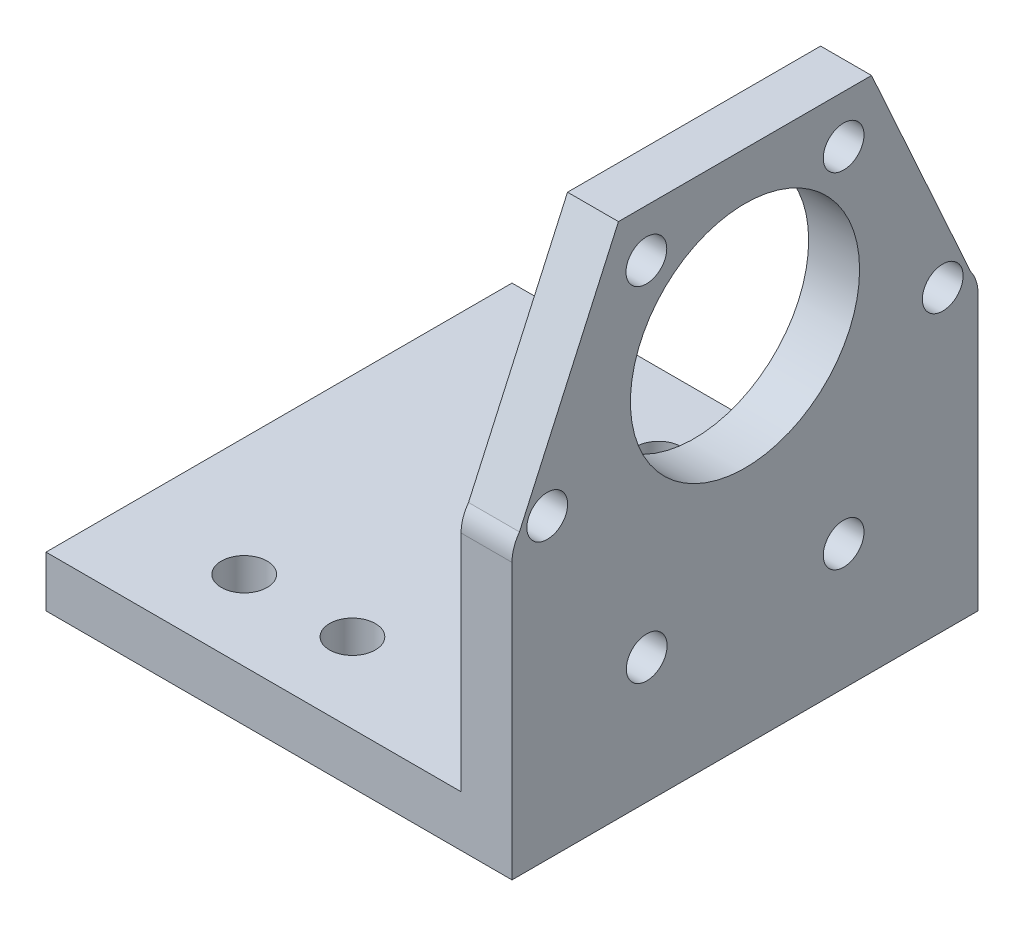
SolidWorks part; units mm, degrees
ref_plane "前视基准面" through (0, 0, 0) normal (0, 0, 1) x (1, 0, 0)
ref_plane "上视基准面" through (0, 0, 0) normal (0, 1, 0) x (1, 0, 0)
ref_plane "右视基准面" through (0, 0, 0) normal (1, 0, 0) x (0, 0, -1)
sketch "草图1" plane through (0, 0, 0) normal (0, 1, 0) x (1, 0, 0)
  line L1 (18.3, -18.3) -> (-18.3, -18.3)
  line L2 (18.3, -18.3) -> (18.3, 18.3)
  line L3 (18.3, 18.3) -> (-18.3, 18.3)
  line L4 (-18.3, -18.3) -> (-18.3, 18.3)
  line L5 (18.3, -18.3) -> (-18.3, 18.3) construction
  line L6 (18.3, 18.3) -> (-18.3, -18.3) construction
  point P0 (0, 0)
  dimension "D1" = 36.6
  dimension "D2" = 36.6
extrude "凸台-拉伸1" add sketch "草图1" along normal blind 40.6
ref_plane "基准面1" through (0, 40.6, 0) normal (0, 1, 0) x (1, 0, 0)
sketch "草图2" plane through (0, 40.6, 0) normal (0, 1, 0) x (1, 0, 0)
  line L0 (-18.3, -18.3) -> (18.3, -18.3) construction
  line L1 (-18.3, 18.3) -> (14.3, 18.3)
  line L2 (-18.3, 18.3) -> (-18.3, -18.3)
  line L3 (-18.3, -18.3) -> (14.3, -18.3)
  line L4 (14.3, 18.3) -> (14.3, -18.3)
  dimension "D1" = 32.6
extrude "切除-拉伸1" cut sketch "草图2" against normal blind 36.6
ref_plane "基准面2" through (18.3, 0, 0) normal (1, 0, 0) x (0, 0, -1)
sketch "草图3" plane through (18.3, 0, 0) normal (1, 0, 0) x (0, 0, -1)
  line L0 (20.13, 40.6) -> (-20.13, 40.6) construction
  line L1 (-18.3, 40.6) -> (18.3, 40.6)
  line L2 (-18.3, 40.6) -> (-18.3, 4)
  line L3 (-18.3, 4) -> (18.3, 4)
  line L4 (18.3, 40.6) -> (18.3, 4)
  line L5 (-18.3, 40.6) -> (-18.3, 0) construction
  line L6 (18.3, 40.6) -> (18.3, 0) construction
  line L7 (0, 40.6) -> (0, 36.8637) construction
  line L8 (0, 36.8637) -> (0, 27.8637) construction
  line L9 (7.7452, 36.8637) -> (-7.7452, 36.8637)
  line L10 (-7.7452, 36.8637) -> (-15.53, 23.3801) construction
  line L11 (7.7452, 36.8637) -> (15.53, 23.3801) construction
  line L12 (-15.53, 23.3801) -> (-7.719, 9.851) construction
  line L13 (-7.719, 9.851) -> (7.7452, 9.851) construction
  line L14 (7.7452, 9.851) -> (15.53, 23.3801) construction
  circle A0 centre (0, 27.8637) radius 9
  circle A1 centre (-7.7452, 36.8637) radius 1.6
  circle A2 centre (7.7452, 36.8637) radius 1.6
  circle A3 centre (-15.53, 23.3801) radius 1.6
  circle A4 centre (15.53, 23.3801) radius 1.6
  circle A5 centre (7.7452, 9.851) radius 1.6
  circle A6 centre (-7.719, 9.851) radius 1.6
  point P10 (0, 40.6)
  point P20 (0, 36.8637)
  dimension "D2" = 120
  dimension "D4" = 18
  dimension "D1" = 36.6
  dimension "D3" = 120
extrude "切除-拉伸5" cut sketch "草图3" against normal blind 36.6 contours A0 | A1 | A3 | A2 | A4 | A5 | A6 region at (18.3, 27.8637, 0) region at (18.3, 36.8637, 9.3) region at (18.3, 38.4184, -7.7452) region at (18.3, 23.3801, 15.53) region at (18.3, 23.3801, -15.53) region at (18.3, 9.851, -7.7452) region at (18.3, 9.851, 7.719)
fillet "圆角2" radius 2 2 edges at (16.3, 40.6, 18.3) (16.3, 40.6, -18.3)
ref_plane "基准面3" through (0, 0, 0) normal (0, -1, 0) x (-1, 0, 0)
sketch "草图7" plane through (0, 0, 0) normal (0, -1, 0) x (-1, 0, 0)
  line L0 (-18.0079, 0) -> (18.3, 0) construction
  line L1 (18.3, 18.3) -> (18.3, -18.3) construction
  circle A0 centre (0.5074, 12.025) radius 1.8
  circle A1 centre (9.0074, 12.025) radius 1.8
  circle A2 centre (9.0074, -12.025) radius 1.8
  circle A3 centre (0.5074, -12.025) radius 1.8
  dimension "D1" = 8.5
  dimension "D2" = 24.05
extrude "切除-拉伸6" cut sketch "草图7" against normal blind 10
sketch "草图12" plane through (18.3, 0, 0) normal (1, 0, 0) x (0, 0, -1)
  line L0 (-9.3452, 36.8637) -> (-18.3, 36.8637) construction
  line L1 (-18.3, 38.6) -> (-18.3, 0) construction
  line L2 (-17.13, 23.3801) -> (-18.3, 23.3801) construction
  line L3 (-17.715, 23.3801) -> (-11.6264, 36.8637)
  line L4 (-11.6264, 36.8637) -> (-9.9392, 40.6)
  line L5 (2.2, 40.6) -> (-2.2, 40.6) construction
  line L6 (-17.715, 23.3801) -> (-18.3, 23.3801)
  line L7 (-18.3, 23.3801) -> (-18.3, 40.6)
  line L8 (-18.3, 40.6) -> (-9.9392, 40.6)
  line L9 (0, 40.6) -> (0, 22.4035) construction
  line L10 (18.3, 23.3801) -> (18.3, 40.6)
  line L11 (17.715, 23.3801) -> (18.3, 23.3801)
  line L12 (17.715, 23.3801) -> (11.6264, 36.8637)
  line L13 (11.6264, 36.8637) -> (9.9392, 40.6)
  line L14 (18.3, 40.6) -> (9.9392, 40.6)
  circle A0 centre (-7.7452, 36.8637) radius 1.6 construction
  circle A1 centre (-15.53, 23.3801) radius 1.6 construction
  point P12 (-17.715, 23.3801)
  point P13 (-13.8226, 36.8637)
extrude "切除-拉伸8" cut sketch "草图12" against normal blind 10
fillet "圆角5" radius 3 1 edges at (16.3, 23.3801, 18.3)
fillet "圆角6" radius 3 1 edges at (16.3, 23.3801, -18.3)
